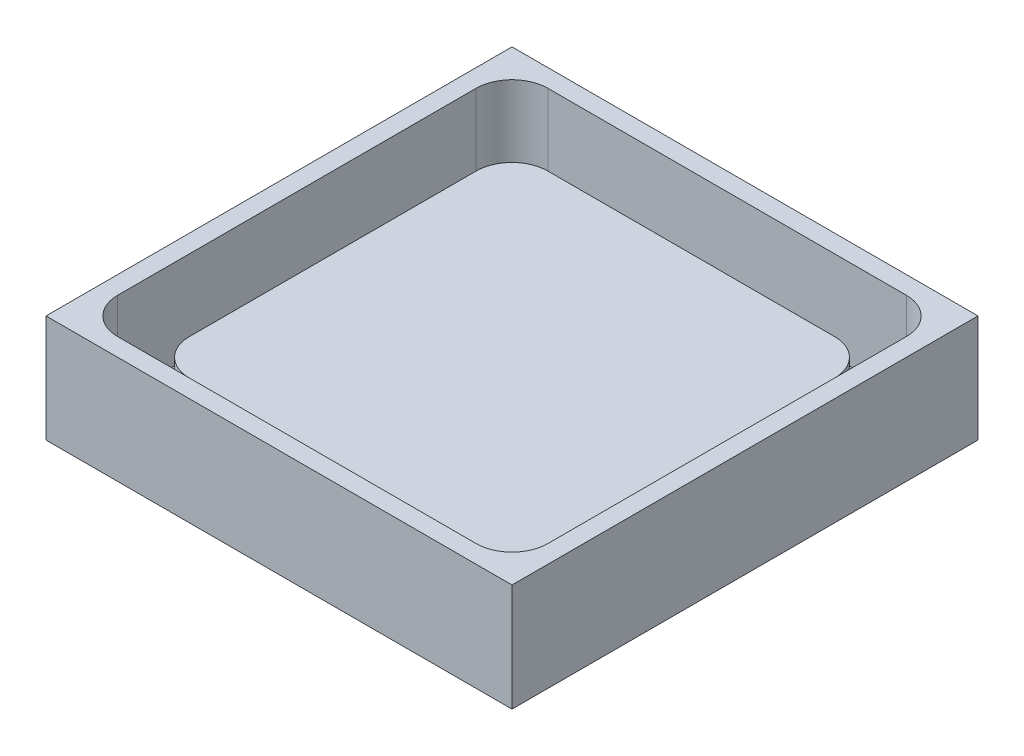
SolidWorks part; units mm, degrees
ref_plane "Front Plane" through (0, 0, 0) normal (0, 0, 1) x (1, 0, 0)
ref_plane "Top Plane" through (0, 0, 0) normal (0, 1, 0) x (1, 0, 0)
ref_plane "Right Plane" through (0, 0, 0) normal (1, 0, 0) x (0, 0, -1)
sketch "Sketch1" plane through (0, 0, 0) normal (0, 1, 0) x (1, 0, 0)
  line L1 (-10, -10) -> (10, -10)
  line L2 (-10, -10) -> (-10, 10)
  line L3 (-10, 10) -> (10, 10)
  line L4 (10, -10) -> (10, 10)
  line L5 (-10, -10) -> (10, 10) construction
  line L6 (-10, 10) -> (10, -10) construction
  point P0 (0, 0)
  dimension "D1" = 20
  dimension "D2" = 20
extrude "Boss-Extrude1" add sketch "Sketch1" along normal blind 4
sketch "Sketch2" plane through (0, 0, 0) normal (0, 1, 0) x (1, 0, 0)
  line L1 (-12, -12) -> (12, -12)
  line L2 (-12, -12) -> (-12, 12)
  line L3 (-12, 12) -> (12, 12)
  line L4 (12, -12) -> (12, 12)
  line L5 (-12, -12) -> (12, 12) construction
  line L6 (-12, 12) -> (12, -12) construction
  line L7 (-13, -13) -> (13, -13)
  line L8 (-13, -13) -> (-13, 13)
  line L9 (-13, 13) -> (13, 13)
  line L10 (13, -13) -> (13, 13)
  line L11 (-13, -13) -> (13, 13) construction
  line L12 (-13, 13) -> (13, -13) construction
  point P0 (0, 0)
  point P6 (0, 0)
  dimension "D1" = 24
  dimension "D2" = 24
  dimension "D3" = 26
  dimension "D4" = 26
extrude "Boss-Extrude2" add sketch "Sketch2" along normal blind 1 contours L2 L1 L4 L3
extrude "Boss-Extrude3" add sketch "Sketch2<3>" along normal blind 6
sketch "Sketch2<3>" plane through (0, 0, 0) normal (0, 1, 0) x (1, 0, 0) same geometry as "Sketch2"
fillet "Fillet1" radius 2 4 edges at (-10, 2.5, 10) (10, 2.5, 10) (10, 2.5, -10) (-10, 2.5, -10)
fillet "Fillet2" radius 2 4 edges at (12, 3.5, 12) (-12, 3.5, 12) (12, 3.5, -12) (-12, 3.5, -12)
